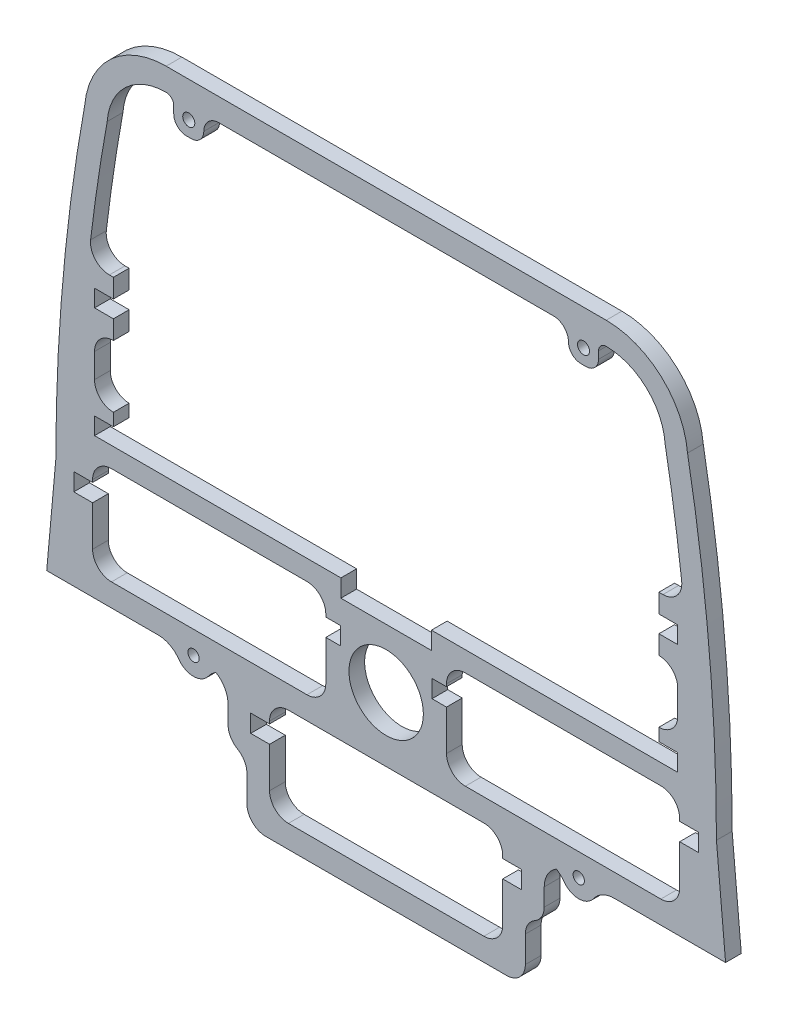
SolidWorks part; units mm, degrees
material "Delrin 2700 NC010, Low Viscosity Acetal Copolymer (SS)"
ref_plane "Front Plane" through (0, 0, 0) normal (0, 0, 1) x (1, 0, 0)
ref_plane "Top Plane" through (0, 0, 0) normal (0, 1, 0) x (1, 0, 0)
ref_plane "Right Plane" through (0, 0, 0) normal (1, 0, 0) x (0, 0, -1)
sketch "Sketch1" plane through (0, 0, 0) normal (0, 0, 1) x (1, 0, 0)
  line L0 (33.3676, -11.9888) -> (34.29, -22.225)
  line L1 (22.225, 27.94) -> (-22.225, 27.94)
  line L2 (-34.29, -22.225) -> (-30.4467, 20.4259) construction
  line L3 (-33.3676, -11.9888) -> (-33.3676, 14.6458) construction
  line L4 (-33.3676, -11.9888) -> (-34.29, -22.225)
  line L5 (16.9079, 25.654) -> (-16.9079, 25.654)
  line L6 (6.096, -13.97) -> (6.096, -19.939)
  line L7 (-29.6529, -19.939) -> (-6.096, -19.939)
  line L8 (-34.29, -22.225) -> (-21.299, -22.225)
  line L9 (-29.6529, -10.033) -> (-29.6529, -12.192)
  line L10 (18.4213, 24.1407) -> (18.4213, 24.1363)
  line L11 (19.6913, 22.8663) -> (20.1867, 22.8663)
  line L12 (21.4567, 24.1363) -> (21.4567, 24.8713)
  line L13 (-21.4567, 24.1363) -> (-21.4567, 24.8713)
  line L14 (-19.6913, 22.8663) -> (-20.1867, 22.8663)
  line L15 (-18.4213, 24.1407) -> (-18.4213, 24.1363)
  line L16 (29.4572, -8.001) -> (4.572, -8.001)
  line L17 (29.6529, -10.033) -> (6.096, -10.033)
  line L18 (0, 18.415) -> (0, -18.415) construction
  line L19 (-1007.9925, 0) -> (48992.0075, 0) construction
  line L20 (-6.096, -10.033) -> (-29.6529, -10.033)
  line L21 (19.939, 24.384) -> (21.4567, 24.384) construction
  line L22 (6.096, -19.939) -> (29.6529, -19.939)
  line L23 (-6.096, -10.033) -> (-6.096, -12.192)
  line L24 (5.9491, -2.2098) -> (59.5431, -2.2098) construction
  line L25 (5.9491, -2.2098) -> (5.9491, -11.9888) construction
  line L26 (3.4091, -11.9888) -> (-3.4091, -11.9888) construction
  line L27 (59.5431, -2.2098) -> (59.5431, -11.9888) construction
  line L28 (-31.7887, -19.939) -> (31.7887, -19.939) construction
  line L29 (22.225, 25.654) -> (-22.225, 25.654) construction
  line L30 (-6.096, -19.939) -> (-6.1666, -19.9899)
  line L31 (29.4572, -6.2738) -> (27.5522, -6.2738)
  line L32 (27.5522, -6.2738) -> (27.5522, -5.0038)
  line L33 (-29.6529, -12.192) -> (-31.5579, -12.192)
  line L34 (27.5522, -5.0038) -> (29.4572, -5.0038)
  line L35 (29.4572, 1.27) -> (27.5522, 1.27)
  line L36 (27.5522, 1.27) -> (27.5522, 3.175)
  line L37 (27.5522, 3.175) -> (29.4572, 3.175)
  line L38 (29.4572, 4.9022) -> (27.5522, 4.9022)
  line L39 (19.939, 24.384) -> (18.4213, 24.384) construction
  line L40 (27.5522, 4.9022) -> (27.5522, 6.8072)
  line L41 (27.5522, 6.8072) -> (30.0922, 6.8072)
  line L42 (19.939, 24.384) -> (19.939, 22.8663) construction
  line L43 (6.096, -10.033) -> (6.096, -12.192)
  line L44 (-29.4572, -6.2738) -> (-29.4572, -8.001)
  line L45 (-29.4572, -6.2738) -> (-27.5522, -6.2738)
  line L46 (-27.5522, -6.2738) -> (-27.5522, -5.0038)
  line L47 (-27.5522, -5.0038) -> (-29.4572, -5.0038)
  line L48 (-29.4572, 1.27) -> (-29.4572, -5.0038)
  line L49 (-29.4572, 1.27) -> (-27.5522, 1.27)
  line L50 (-27.5522, 1.27) -> (-27.5522, 3.175)
  line L51 (-27.5522, 3.175) -> (-29.4572, 3.175)
  line L52 (-29.4572, 4.9022) -> (-29.4572, 3.175)
  line L53 (-31.5579, -12.192) -> (-31.5579, -13.97)
  line L54 (-31.5579, -13.97) -> (-29.6529, -13.97)
  line L55 (-6.096, -12.192) -> (-4.6339, -12.192)
  line L56 (-4.6339, -12.192) -> (-4.6339, -13.97)
  line L57 (-4.6339, -13.97) -> (-6.096, -13.97)
  line L58 (-29.6529, -10.033) -> (-29.6529, -19.939) construction
  line L59 (-29.6529, -14.986) -> (-33.4249, -14.986) construction
  line L60 (-29.6529, -14.986) -> (-0.4824, -14.986) construction
  line L61 (-6.096, -13.97) -> (-6.096, -19.939)
  line L62 (-29.6529, -19.939) -> (-29.6529, -13.97)
  line L63 (29.6529, -19.939) -> (29.6529, -13.97)
  line L64 (-31.0816, -12.0913) -> (-31.7887, -19.939) construction
  line L65 (29.6529, -10.033) -> (29.6529, -12.192)
  line L66 (31.5579, -13.97) -> (29.6529, -13.97)
  line L67 (31.5579, -12.192) -> (31.5579, -13.97)
  line L68 (29.6529, -12.192) -> (31.5579, -12.192)
  line L69 (6.096, -12.192) -> (4.6339, -12.192)
  line L70 (4.6339, -12.192) -> (4.6339, -13.97)
  line L71 (4.6339, -13.97) -> (6.096, -13.97)
  line L72 (29.4572, 4.9022) -> (29.4572, 3.175)
  line L73 (31.0816, -12.0913) -> (31.7887, -19.939) construction
  line L74 (29.4572, 1.27) -> (29.4572, -5.0038)
  line L75 (29.4572, -6.2738) -> (29.4572, -8.001)
  line L76 (-29.4572, 4.9022) -> (-27.5522, 4.9022)
  line L77 (-27.5522, 4.9022) -> (-27.5522, 6.8072)
  line L78 (-27.5522, 6.8072) -> (-30.0922, 6.8072)
  line L79 (-17.616, -22.225) -> (-15.9694, -22.225)
  line L80 (21.299, -22.225) -> (34.29, -22.225)
  line L81 (-34.29, -22.225) -> (34.29, -22.225) construction
  line L82 (-4.572, -8.001) -> (-4.572, -9.779)
  line L83 (-4.572, -9.779) -> (0, -9.779)
  line L84 (0, -9.779) -> (4.572, -9.779)
  line L85 (4.572, -9.779) -> (4.572, -8.001)
  line L86 (-4.572, -8.001) -> (-29.4572, -8.001)
  line L87 (-11.7784, -22.225) -> (-11.7784, -24.384)
  line L88 (-11.7784, -24.384) -> (-13.6834, -24.384)
  line L89 (-13.6834, -24.384) -> (-13.6834, -26.162)
  line L90 (-13.6834, -26.162) -> (-11.7784, -26.162)
  line L91 (-11.7784, -26.162) -> (-11.7784, -32.131)
  line L92 (-11.7784, -32.131) -> (11.7784, -32.131)
  line L93 (11.7784, -32.131) -> (11.7784, -26.162)
  line L94 (11.7784, -26.162) -> (13.6834, -26.162)
  line L95 (13.6834, -26.162) -> (13.6834, -24.384)
  line L96 (13.6834, -24.384) -> (11.7784, -24.384)
  line L97 (11.7784, -24.384) -> (11.7784, -22.225)
  line L98 (11.7784, -22.225) -> (-11.7784, -22.225) construction
  line L99 (0, -32.131) -> (0, -22.225) construction
  line L100 (-11.7784, -22.225) -> (11.7784, -22.225)
  line L101 (-15.9694, -22.098) -> (-15.9694, -28.448) construction
  line L102 (-15.9694, -22.225) -> (-15.9694, -28.448)
  line L103 (-15.9694, -28.448) -> (-14.0644, -28.448)
  line L104 (-14.0644, -28.448) -> (-14.0644, -34.417)
  line L105 (-14.0644, -34.417) -> (14.0644, -34.417)
  line L106 (14.0644, -34.417) -> (14.0644, -28.448)
  line L107 (14.0644, -28.448) -> (15.9694, -28.448)
  line L108 (15.9694, -28.448) -> (15.9694, -22.225)
  line L109 (15.9694, -22.225) -> (17.616, -22.225)
  line L110 (15.9694, -28.448) -> (15.9694, -22.098) construction
  line L111 (15.9694, -22.098) -> (14.0609, -22.098) construction
  line L112 (14.0609, -22.098) -> (14.0609, -22.098) construction
  line L113 (-14.0609, -22.098) -> (-14.0609, -22.098) construction
  line L114 (-14.0609, -22.098) -> (-15.9694, -22.098) construction
  arc A0 (22.225, 27.94) -> (30.4467, 20.4259) centre (22.225, 19.685) cw
  arc A1 (-22.225, 27.94) -> (-30.4467, 20.4259) centre (-22.225, 19.685) ccw
  arc A2 (33.3676, -11.9888) -> (30.4467, 20.4259) centre (-147.9525, -11.9888) ccw
  circle A3 centre (0, -15.748) radius 3.7592
  circle A4 centre (19.4575, -22.225) radius 0.5715
  arc A5 (-33.3676, -11.9888) -> (-30.4467, 20.4259) centre (147.9525, -11.9888) cw
  arc A6 (-17.616, -22.225) -> (-21.299, -22.225) centre (-19.4575, -22.225) cw
  arc A7 (17.616, -22.225) -> (21.299, -22.225) centre (19.4575, -22.225) ccw
  arc A8 (20.1867, 22.8663) -> (21.4567, 24.1363) centre (20.1867, 24.1363) ccw
  circle A9 centre (-19.939, 24.384) radius 0.6096
  circle A10 centre (19.939, 24.384) radius 0.6096
  arc A11 (18.4213, 24.1363) -> (19.6913, 22.8663) centre (19.6913, 24.1363) ccw
  circle A12 centre (-19.4575, -22.225) radius 0.5715
  arc A13 (18.4213, 24.1407) -> (16.9079, 25.654) centre (16.9079, 24.1407) ccw
  arc A14 (22.2416, 25.654) -> (21.4567, 24.8713) centre (22.2394, 24.8713) ccw
  arc A15 (-22.2416, 25.654) -> (-21.4567, 24.8713) centre (-22.2394, 24.8713) cw
  arc A16 (-20.1867, 22.8663) -> (-21.4567, 24.1363) centre (-20.1867, 24.1363) cw
  arc A17 (-18.4213, 24.1363) -> (-19.6913, 22.8663) centre (-19.6913, 24.1363) cw
  arc A18 (-22.2416, 25.654) -> (-28.1777, 20.1262) centre (-22.225, 19.685) ccw
  arc A19 (-18.4213, 24.1407) -> (-16.9079, 25.654) centre (-16.9079, 24.1407) cw
  arc A20 (31.0816, -12.0913) -> (31.0816, -11.9888) centre (-147.9525, -11.9888) ccw
  circle A21 centre (-19.4575, -22.225) radius 1.8415 construction
  arc A23 (22.2416, 25.654) -> (28.1777, 20.1262) centre (22.225, 19.685) cw
  arc A25 (-22.225, 25.654) -> (-28.1777, 20.1262) centre (-22.225, 19.685) ccw construction
  arc A26 (22.225, 25.654) -> (28.1777, 20.1262) centre (22.225, 19.685) cw construction
  arc A28 (-31.0816, -12.0913) -> (-28.1777, 20.1262) centre (147.9525, -11.9888) cw construction
  arc A30 (31.0816, -12.0913) -> (28.1777, 20.1262) centre (-147.9525, -11.9888) ccw construction
  arc A31 (30.0922, 6.8072) -> (28.1777, 20.1262) centre (-147.9525, -11.9888) ccw
  arc A33 (-30.0922, 6.8072) -> (-28.1777, 20.1262) centre (147.9525, -11.9888) cw
  point P0 (0, 0)
  point P1 (0, 27.94)
  point P31 (0, -11.9888)
  point P121 (-30.9018, -14.986)
  point P135 (-17.616, -22.225)
  dimension "D4" = 2.286
  dimension "D6" = 8.255
  dimension "D7" = 19.4575
  dimension "D8" = 50.165
  dimension "D9" = 15.748
  dimension "D5" = 1.2192
  dimension "D17" = 1.143
  dimension "D3" = 7.5184
  dimension "D18" = 1.27
  dimension "D19" = 1.27
  dimension "D26" = 11.176
  dimension "D28" = 0.7827
  dimension "D29" = 1.5133
  dimension "D32" = 1.905
  dimension "D2" = 44.45
  dimension "D10" = 1.27
  dimension "D11" = 1.27
  dimension "D12" = 68.58
  dimension "D13" = 19.939
  dimension "D14" = 22.225
  dimension "D15" = 53.594
  dimension "D16" = 9.779
  dimension "D20" = 6.096
  dimension "D21" = 11.938
  dimension "D22" = 2.032
  dimension "D23" = 1.7272
  dimension "D24" = 1.27
  dimension "D25" = 1.905
  dimension "D27" = 0.4954
  dimension "D30" = 1.905
  dimension "D31" = 1.7272
  dimension "D33" = 1.778
  dimension "D34" = 2.159
  dimension "D35" = 23.5569
  dimension "D36" = 26.924
  dimension "D37" = 1.905
  dimension "D38" = 2.54
  dimension "D39" = 1.778
  dimension "D40" = 9.144
  dimension "D41" = 2.286
extrude "Boss-Extrude1" add sketch "Sketch1" along normal blind 1.5875 contours L8 A12 A4 L0 A2 A0 L1 A1 A5 L4 L74 L16 A18 A15 L13 A16 L14 A17 L15 A19 L5 A13 L10 A11 L11 A8 L12 A14 A23 A20 L22 L43 L17 A10 A9 A3 L20 region at (32.9056, -17.1901, 0)
ref_axis "Axis1" through (0, -15.748, 0) along (0, 0, 1)
fillet "Fillet1" radius 1.905 12 edges at (-6.096, -10.033, 0.7937) (6.096, -10.033, 0.7937) (-6.096, -19.939, 0.7937) (-29.6529, -19.939, 0.7937) (-29.6529, -10.033, 0.7937) (6.096, -19.939, 0.7937) (29.6529, -19.939, 0.7937) (29.6529, -10.033, 0.7937) (11.7784, -32.131, 0.7937) (11.7784, -22.225, 0.7937) (-11.7784, -32.131, 0.7937) (-11.7784, -22.225, 0.7937)
fillet "Fillet2" radius 1.905 6 edges at (-29.4572, 1.27, 0.7937) (-29.4572, -5.0038, 0.7937) (-30.0922, 6.8072, 0.7937) (29.4572, -5.0038, 0.7937) (29.4572, 1.27, 0.7937) (30.0922, 6.8072, 0.7937)
fillet "Fillet3" radius 2.54 6 edges at (-17.616, -22.225, 0.7937) (-21.299, -22.225, 0.7937) (21.299, -22.225, 0.7937) (17.616, -22.225, 0.7937) (15.9694, -22.225, 0.7937) (-15.9694, -22.225, 0.7937)
fillet "Fillet4" radius 1.905 4 edges at (15.9694, -28.448, 0.7937) (14.0644, -34.417, 0.7937) (-14.0644, -34.417, 0.7937) (-15.9694, -28.448, 0.7937)
fillet "Fillet5" radius 1.905 2 edges at (14.0644, -28.448, 0.7937) (-14.0644, -28.448, 0.7937)
